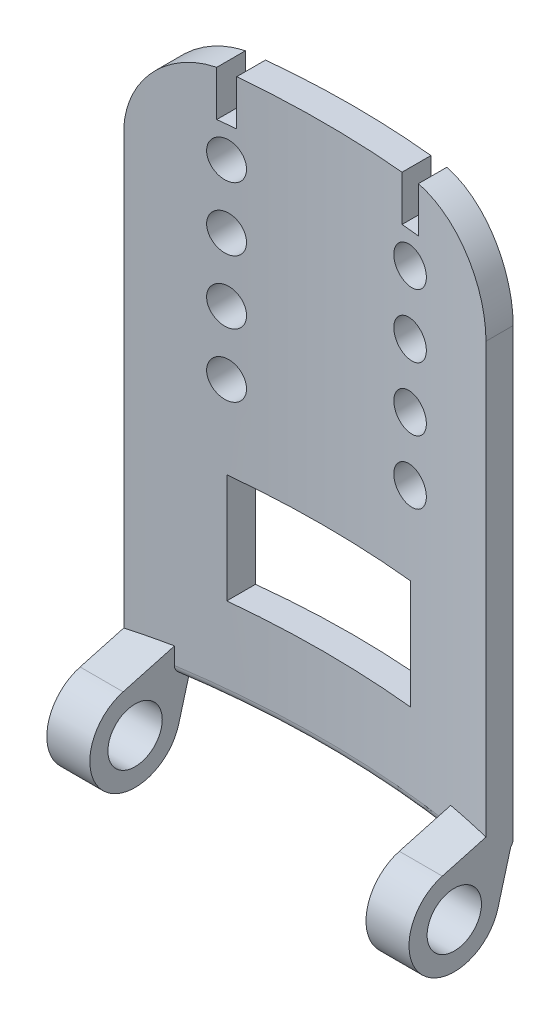
SolidWorks part; units mm, degrees
ref_plane "前视基准面" through (0, 0, 0) normal (0, 0, 1) x (1, 0, 0)
ref_plane "上视基准面" through (0, 0, 0) normal (0, 1, 0) x (1, 0, 0)
ref_plane "右视基准面" through (0, 0, 0) normal (1, 0, 0) x (0, 0, -1)
other "Configuration Table"
sketch "草图1" plane through (0, 0, 0) normal (0, 1, 0) x (1, 0, 0)
  line L0 (-20, 0) -> (20, 0) construction
  line L1 (-20, 0) -> (-20, 3)
  line L2 (20, 0) -> (20, 3)
  arc A0 (-20, 0) -> (20, 0) centre (0, -97.9796) cw
  arc A1 (-20, 3) -> (20, 3) centre (0, -84.7496) cw
  point P7 (0, 0)
  dimension "D1" = 100
  dimension "D5" = 90
  dimension "D2" = 3
  dimension "D3" = 3
  dimension "D4" = 40
extrude "凸台-拉伸2" add sketch "草图1" along normal blind 60
sketch "草图2" plane through (20, 0, 0) normal (1, 0, 0) x (0, 0, -1)
  line L0 (1.5, 1.5) -> (3, 1.5) construction
  line L1 (3, 60) -> (3, 0) construction
  line L2 (1.5, 1.5) -> (1.5, 0) construction
  line L3 (0, 0) -> (3, 0) construction
  line L4 (1.1034, 2.9466) -> (-4.8221, 1.3221)
  line L7 (-4.8221, 1.3221) -> (-3.5, -3.5) construction
  line L8 (1.3221, -4.8221) -> (2.9466, 1.1034)
  line L9 (-3.5, -3.5) -> (1.3221, -4.8221) construction
  line L10 (1.5, 1.5) -> (-3.5, -3.5) construction
  arc A0 (2.9466, 1.1034) -> (1.1034, 2.9466) centre (1.5, 1.5) ccw
  arc A1 (1.1034, 2.9466) -> (2.9466, 1.1034) centre (1.5, 1.5) ccw construction
  arc A2 (-4.8221, 1.3221) -> (1.3221, -4.8221) centre (-3.5, -3.5) ccw
  circle A3 centre (-3.5, -3.5) radius 3
  dimension "D1" = 3
  dimension "D4" = 6
  dimension "D5" = 2
  dimension "D2" = 135
  dimension "D3" = 5
extrude "凸台-拉伸3" add sketch "草图2" against normal blind 4.75
mirror "镜向1" about plane through (0, 0, 0) normal (1, 0, 0) of "凸台-拉伸3"
sketch "草图3" plane through (0, 0, 0) normal (0, 0, 1) x (1, 0, 0)
  line L0 (-11.1324, 60) -> (-11.1324, 55)
  line L1 (20, 60) -> (-20, 60) construction
  line L2 (-11.1324, 55) -> (-9.1324, 55)
  line L3 (-9.1324, 55) -> (-9.1324, 60)
  line L4 (-9.1324, 60) -> (-11.1324, 60)
  line L5 (0, -1000.495) -> (0, 48999.505) construction
  line L10 (-10.1324, 55) -> (-10.1324, 30.5939) construction
  line L11 (10.1324, 55) -> (10.1324, 30.5939) construction
  line L12 (9.1324, 60) -> (11.1324, 60)
  line L13 (9.1324, 55) -> (9.1324, 60)
  line L14 (11.1324, 55) -> (9.1324, 55)
  line L15 (11.1324, 60) -> (11.1324, 55)
  line L16 (-10.1324, 21.4779) -> (10.1324, 21.4779)
  line L17 (10.1324, 21.4779) -> (10.1324, 9.4116)
  line L18 (10.1324, 9.4116) -> (-10.1324, 9.4116)
  line L19 (-10.1324, 9.4116) -> (-10.1324, 21.4779)
  circle A0 centre (-10.1324, 30.5939) radius 2
  circle A1 centre (10.1324, 30.5939) radius 2
  circle A2 centre (-10.1324, 37.5939) radius 2
  circle A3 centre (10.1324, 37.5939) radius 2
  circle A4 centre (-10.1324, 44.5939) radius 2
  circle A5 centre (10.1324, 44.5939) radius 2
  circle A6 centre (-10.1324, 51.5939) radius 2
  circle A7 centre (10.1324, 51.5939) radius 2
  dimension "D3" = 4
  dimension "D1" = 2
  dimension "D2" = 5
  dimension "D4" = 4
extrude "切除-拉伸1" cut sketch "草图3" against normal through all both and the other way through all
fillet "圆角1" radius 10 2 edges at (20, 60, -1.5) (-20, 60, -1.5)
fillet "圆角4" radius 1 2 edges at (0, 0, -5.2504) (0, 0, -2.0204)
